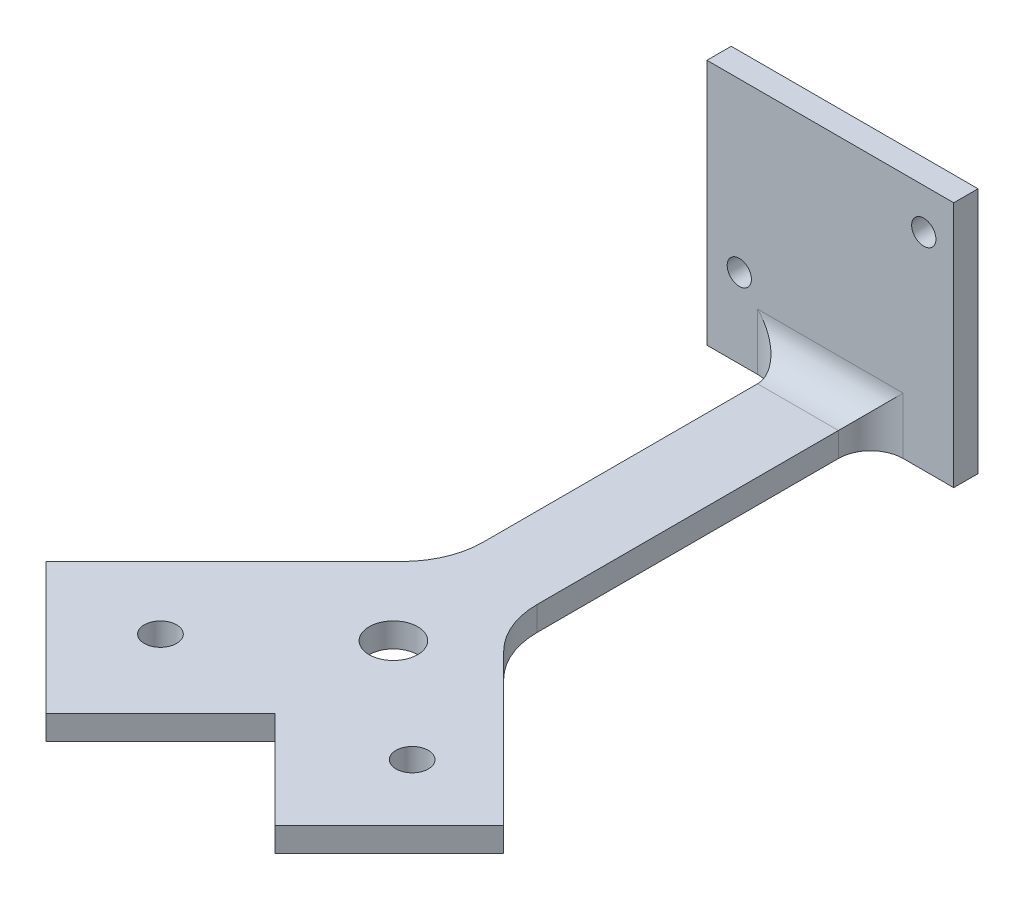
SolidWorks part; units mm, degrees
ref_plane "Płaszczyzna przednia" through (0, 0, 0) normal (0, 0, 1) x (1, 0, 0)
ref_plane "Płaszczyzna górna" through (0, 0, 0) normal (0, 1, 0) x (1, 0, 0)
ref_plane "Płaszczyzna prawa" through (0, 0, 0) normal (1, 0, 0) x (0, 0, -1)
sketch "Sketch1" plane through (0, 0, 0) normal (0, 0, 1) x (1, 0, 0)
  line L1 (0, 0) -> (30.5, 0)
  line L2 (0, 0) -> (0, 30.5)
  line L3 (0, 30.5) -> (30.5, 30.5)
  line L4 (30.5, 0) -> (30.5, 30.5)
  line L5 (0, 0) -> (30.5, 30.5) construction
  line L6 (0, 30.5) -> (30.5, 0) construction
  point P4 (15.25, 15.25)
  dimension "D1" = 30.5
  dimension "D2" = 30.5
extrude "Boss-Extrude1" add sketch "Sketch1" along normal blind 3
sketch "Sketch2" plane through (0, 0, 0) normal (0, -1, 0) x (1, 0, 0)
  line L0 (0, 3) -> (30.5, 3) construction
  line L1 (10.25, 3) -> (20.25, 3)
  line L2 (10.25, 3) -> (10.25, 63)
  line L3 (10.25, 63) -> (20.25, 63)
  line L4 (20.25, 3) -> (20.25, 63)
  line L5 (10.25, 3) -> (20.25, 63) construction
  line L6 (10.25, 63) -> (20.25, 3) construction
  line L7 (0, 3) -> (0, 0) construction
  point P4 (15.25, 33)
  dimension "D1" = 60
  dimension "D2" = 10
  dimension "D3" = 10.25
extrude "Boss-Extrude2" add sketch "Sketch2" against normal blind 3
sketch "Sketch3" plane through (0, 0, 0) normal (0, -1, 0) x (1, 0, 0)
  line L0 (22.5652, 50.6848) -> (13.5845, 41.704)
  line L5 (13.5845, 41.704) -> (-14.6998, 69.9882)
  line L6 (-14.6998, 69.9882) -> (1.5636, 86.2517)
  line L11 (1.5636, 86.2517) -> (15.7058, 72.1096)
  line L12 (15.7058, 72.1096) -> (27.7266, 84.1304)
  line L13 (27.7266, 84.1304) -> (41.8687, 69.9882)
  line L14 (10.25, 63) -> (22.8491, 50.4009) construction
  line L15 (20.25, 63) -> (10.25, 63) construction
  line L16 (41.8687, 69.9882) -> (22.5652, 50.6848)
  dimension "D1" = 20
  dimension "D2" = 17
  dimension "D3" = 40
  dimension "D4" = 40
  dimension "D5" = 45
extrude "Boss-Extrude3" add sketch "Sketch3" against normal blind 3
hole_wizard "Ø3.0mm Dowel Hole1" positions "Sketch4" profile "Sketch5" hole size "Ø3.0" standard "ANSI Metric" end condition up to next
sketch "Sketch4" plane through (0, 0, 3) normal (0, 0, 1) x (1, 0, 0)
  point P0 (4, 9.8)
  point P3 (26.8, 25.5)
sketch "Sketch5" plane through (4, 9.8, 3) normal (1, 0, 0) x (0, -1, 0)
  line L0 (0, 0) -> (0, 3)
  line L1 (0, 3) -> (1.5, 3)
  line L2 (1.5, 3) -> (1.5, 0)
  line L5 (1.5, 0) -> (0, 0)
  line L11 (0, -6.35) -> (0, 107.95) construction
  dimension "Thru Hole Dia." = 3
  dimension "Thru Hole Depth" = 3
fillet "Fillet1" radius 4 3 edges at (20.25, 1.5, 3) (10.25, 1.5, 3) (15.25, 3, 3)
fillet "Fillet2" radius 10 2 edges at (20.25, 1.5, 48.3695) (10.25, 1.5, 45.0384)
sketch "Sketch6" plane through (0, 3, 0) normal (0, 1, 0) x (1, 0, 0)
  line L0 (20.25, -7) -> (20.25, -44.2274) construction
  line L2 (20.25, -7) -> (10.25, -7) construction
  circle A0 centre (15.25, -57) radius 3
  dimension "D1" = 5
  dimension "6" = 6
  dimension "D2" = 50
extrude "Cut-Extrude1" cut sketch "Sketch6" against normal blind 3
hole_wizard "Ø4.0mm Dowel Hole1" positions "Sketch7" profile "Sketch8" hole size "Ø4.0" standard "ANSI Metric" end condition up to next
sketch "Sketch7" plane through (0, 3, 0) normal (0, 1, 0) x (1, 0, 0)
  point P0 (0.1494, -70.6953)
sketch "Sketch8" plane through (0.1494, 3, 70.6953) normal (1, 0, 0) x (0, 0, 1)
  line L0 (0, 0) -> (0, 3)
  line L1 (0, 3) -> (2, 3)
  line L2 (2, 3) -> (2, 0)
  line L5 (2, 0) -> (0, 0)
  line L11 (0, -6.35) -> (0, 107.95) construction
  dimension "Thru Hole Dia." = 4
  dimension "Thru Hole Depth" = 3
hole_wizard "Ø4.0mm Dowel Hole2" positions "Sketch9" profile "Sketch10" hole size "Ø4.0" standard "ANSI Metric" end condition up to next
sketch "Sketch9" plane through (0, 3, 0) normal (0, 1, 0) x (1, 0, 0)
  point P0 (29.1408, -68.574)
sketch "Sketch10" plane through (29.1408, 3, 68.574) normal (1, 0, 0) x (0, 0, 1)
  line L0 (0, 0) -> (0, 3)
  line L1 (0, 3) -> (2, 3)
  line L2 (2, 3) -> (2, 0)
  line L5 (2, 0) -> (0, 0)
  line L11 (0, -6.35) -> (0, 107.95) construction
  dimension "Thru Hole Dia." = 4
  dimension "Thru Hole Depth" = 3
